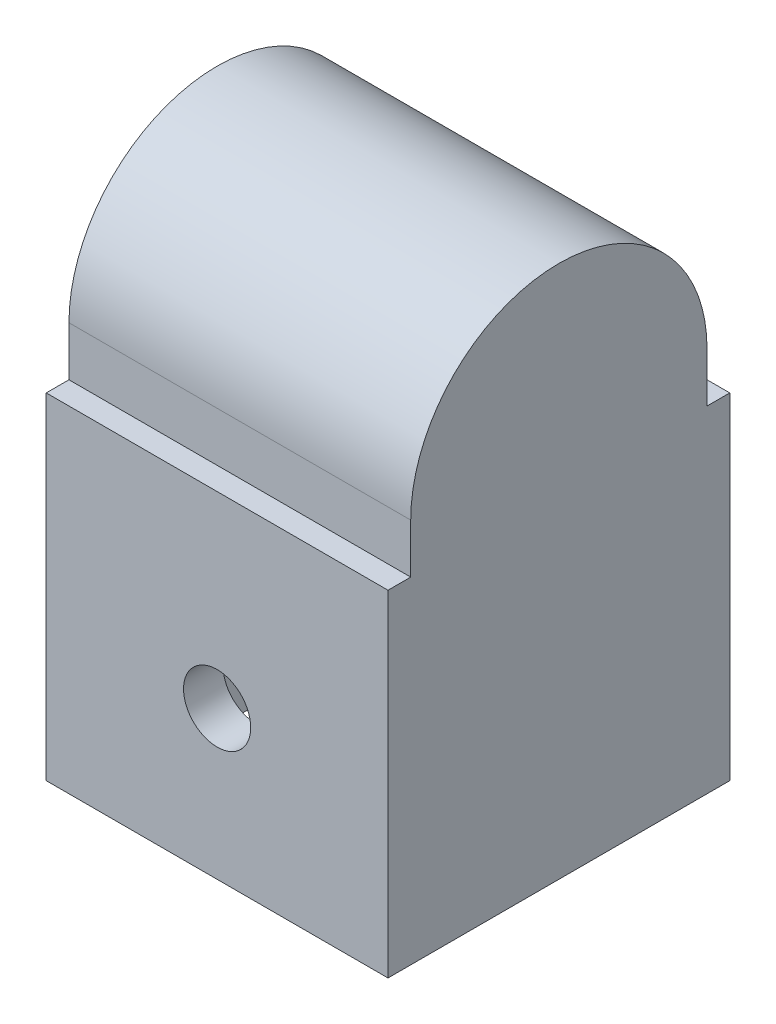
SolidWorks part; units mm, degrees
ref_plane "Alzado" through (0, 0, 0) normal (0, 0, 1) x (1, 0, 0)
ref_plane "Planta" through (0, 0, 0) normal (0, 1, 0) x (1, 0, 0)
ref_plane "Vista lateral" through (0, 0, 0) normal (1, 0, 0) x (0, 0, -1)
sketch "Croquis3" plane through (0, 0, 0) normal (0, 1, 0) x (1, 0, 0)
  line L0 (-8.65, 8.65) -> (8.65, 8.65)
  line L1 (-6.65, -6.65) -> (6.65, -6.65)
  line L2 (-6.65, -6.65) -> (-6.65, 6.65)
  line L3 (-6.65, 6.65) -> (6.65, 6.65)
  line L4 (6.65, -6.65) -> (6.65, 6.65)
  line L5 (-6.65, -6.65) -> (6.65, 6.65) construction
  line L6 (-6.65, 6.65) -> (6.65, -6.65) construction
  line L7 (8.65, -8.65) -> (8.65, 8.65)
  line L8 (-8.65, -8.65) -> (8.65, -8.65)
  line L9 (-8.65, -8.65) -> (-8.65, 8.65)
  point P0 (0, 0)
  dimension "D1" = 13.3
  dimension "D2" = 2
extrude "Saliente-Extruir1" add sketch "Croquis3" against normal blind 15
extrude "Saliente-Extruir2" add sketch "Croquis3<2>" along normal blind 2 contours L9 L8 L7 L0 L4 L1 L2 L3 | L1 L4 L3 L2 region at (0, 0, -8.4053) region at (0, 0, 0)
sketch "Croquis3<2>" plane through (0, 0, 0) normal (0, 1, 0) x (1, 0, 0) same geometry as "Croquis3"
sketch "Croquis5" plane through (0, 0, 0) normal (0, 0, 1) x (1, 0, 0)
  line L0 (0, -15) -> (0, 0) construction
  line L1 (-8.65, -15) -> (8.65, -15) construction
  line L2 (-8.65, -7.5) -> (8.65, -7.5) construction
  line L3 (-8.65, -15) -> (-8.65, 2) construction
  line L4 (8.65, -15) -> (8.65, 2) construction
  circle A0 centre (0, -7.5) radius 1.7
  point P13 (0, -7.5)
  point P14 (0, 0)
  dimension "D1" = 3.4
extrude "Cortar-Extruir1" cut sketch "Croquis5" against normal through all both and the other way through all
sketch "Croquis7" plane through (0, 0, 0) normal (1, 0, 0) x (0, 0, -1)
  line L0 (-7.5, 4.5) -> (-7.5, 2)
  line L1 (-8.65, 2) -> (8.65, 2) construction
  line L2 (-7.5, 2) -> (7.5, 2)
  line L3 (7.5, 2) -> (7.5, 4.5)
  arc A1 (7.5, 4.5) -> (-7.5, 4.5) centre (0, 4.5) ccw
  point P1 (0, 6.7677)
  dimension "D1" = 7.5
  dimension "D2" = 2.5
extrude "Saliente-Extruir4" add sketch "Croquis7" along normal through all and the other way through all
shell "Vaciado1" thickness 2
